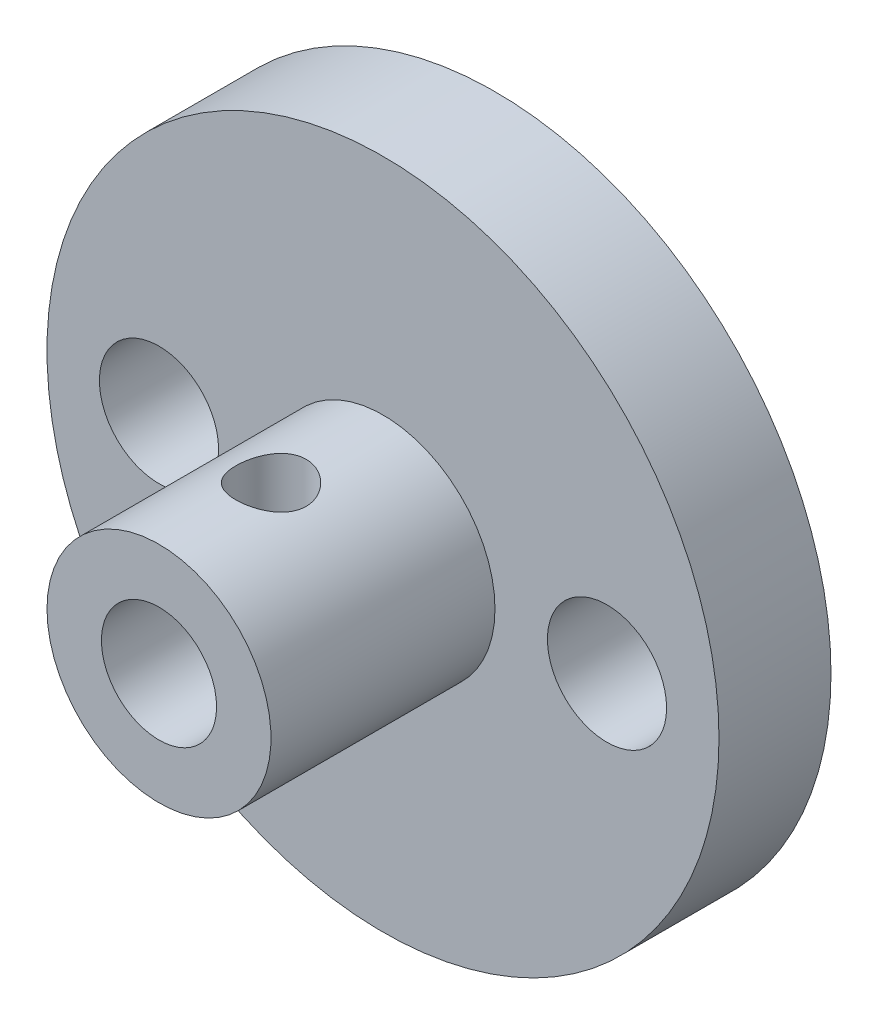
SolidWorks part; units mm, degrees
material "1060 Alloy"
ref_plane "Front" through (0, 0, 0) normal (0, 0, 1) x (1, 0, 0)
ref_plane "Top" through (0, 0, 0) normal (0, 1, 0) x (1, 0, 0)
ref_plane "Right" through (0, 0, 0) normal (1, 0, 0) x (0, 0, -1)
sketch "Sketch1" plane through (0, 0, 0) normal (0, 0, 1) x (1, 0, 0)
  circle A0 centre (0, 0) radius 19.05
  dimension "D1" = 38.1
extrude "Boss-Extrude1" add sketch "Sketch1" along normal blind 6.35
sketch "Sketch2" plane through (0, 0, 0) normal (0, 0, -1) x (-1, 0, 0)
  circle A0 centre (0, 0) radius 6.35
  dimension "D1" = 12.7
extrude "Boss-Extrude2" add sketch "Sketch2" against normal blind 19.05
hole_wizard "F (0.257) Diameter Hole1" positions "Sketch3" profile "Sketch4" hole size "F" standard "ANSI Inch" end condition through all
sketch "Sketch3" plane through (0, 0, 19.05) normal (0, 0, 1) x (1, 0, 0)
  point P0 (0, 0)
sketch "Sketch4" plane through (0, 0, 19.05) normal (1, 0, 0) x (0, -1, 0)
  line L0 (0, 0) -> (0, 19.05)
  line L1 (0, 19.05) -> (3.2639, 19.05)
  line L2 (3.2639, 19.05) -> (3.2639, 0)
  line L5 (3.2639, 0) -> (0, 0)
  line L11 (0, -6.35) -> (0, 107.95) construction
  dimension "Thru Hole Dia." = 6.5278
  dimension "Thru Hole Depth" = 19.05
hole_wizard "#10-24 Tapped Hole3" positions "3DSketch2" profile "Sketch9" tap size "#10-24" standard "ANSI Inch"
sketch3d "3DSketch2"
  point P0 (0, 6.35, 12.7)
  dimension "D1" = 12.7
cosmetic thread "Hole Thread7" parameters "D1"=3.7659, "D2"=4.826
sketch "Sketch9" plane through (0, 6.35, 12.7) normal (1, 0, 0) x (0, 0, 1)
  line L0 (0, 0) -> (0, 7.5471)
  line L1 (0, 7.5471) -> (1.9939, 6.349)
  line L2 (1.9939, 6.349) -> (1.9939, 0)
  line L5 (1.9939, 0) -> (0, 0)
  line L10 (0, 7.5471) -> (-1.9939, 6.349) construction
  line L11 (0, -6.35) -> (0, 107.95) construction
  dimension "Tap Drill Dia." = 3.9878
  dimension "Tap Drill Depth" = 6.349
  dimension "Drill Angle" = 118
sketch "Sketch11" plane through (0, 0, 6.35) normal (0, 0, 1) x (1, 0, 0)
  circle A0 centre (0, 0) radius 12.7 construction
  dimension "D1" = 25.4
hole_wizard "H (0.266) Diameter Hole1" positions "Sketch12" profile "Sketch13" hole size "H" standard "ANSI Inch" end condition through all
sketch "Sketch12" plane through (0, 0, 6.35) normal (0, 0, 1) x (1, 0, 0)
  circle A0 centre (0, 0) radius 12.7 construction
  point P0 (-12.7, 0)
  point P4 (12.7, 0)
sketch "Sketch13" plane through (-12.7, 0, 6.35) normal (1, 0, 0) x (0, -1, 0)
  line L0 (0, 0) -> (0, 6.35)
  line L1 (0, 6.35) -> (3.3782, 6.35)
  line L2 (3.3782, 6.35) -> (3.3782, 0)
  line L5 (3.3782, 0) -> (0, 0)
  line L11 (0, -6.35) -> (0, 107.95) construction
  dimension "Thru Hole Dia." = 6.7564
  dimension "Thru Hole Depth" = 6.35
